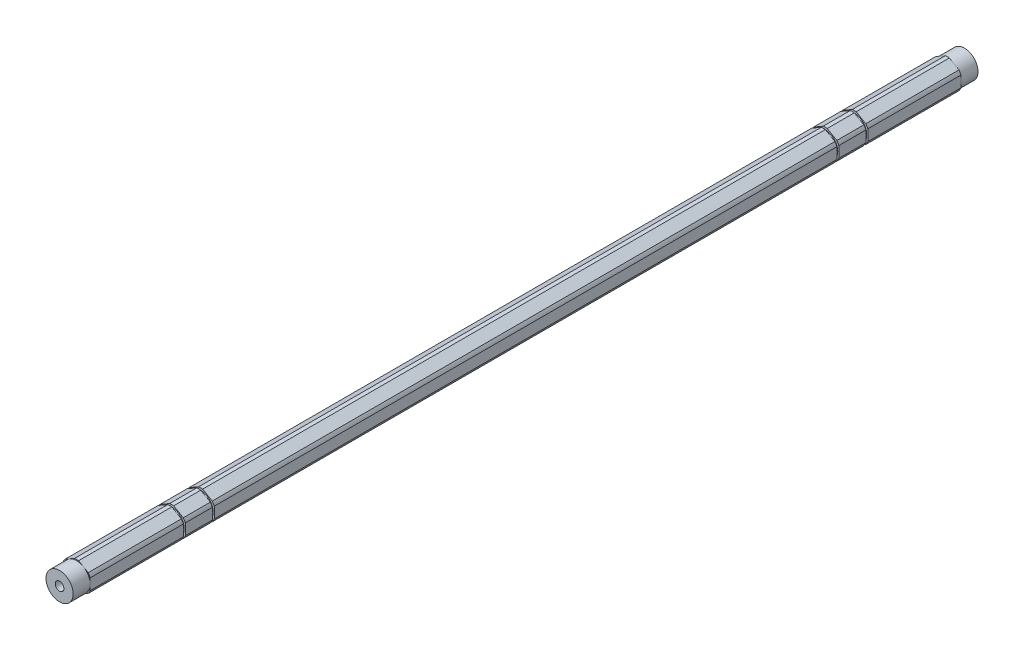
SolidWorks part; units mm, degrees
ref_plane "Front Plane" through (0, 0, 0) normal (0, 0, 1) x (1, 0, 0)
ref_plane "Top Plane" through (0, 0, 0) normal (0, 1, 0) x (1, 0, 0)
ref_plane "Right Plane" through (0, 0, 0) normal (1, 0, 0) x (0, 0, -1)
sketch "Sketch1" plane through (0, 0, 0) normal (0, 0, 1) x (1, 0, 0)
  line L1 (0, 7.3323) -> (-6.35, 3.6662)
  line L2 (-6.35, 3.6662) -> (-6.35, -3.6662)
  line L3 (-6.35, -3.6662) -> (0, -7.3323)
  line L4 (0, -7.3323) -> (6.35, -3.6662)
  line L5 (6.35, -3.6662) -> (6.35, 3.6662)
  line L6 (6.35, 3.6662) -> (0, 7.3323)
  circle A0 centre (0, 0) radius 6.35 construction
  circle A1 centre (0, 0) radius 6.858
  dimension "D1" = 12.7
  dimension "D2" = 13.716
extrude "Boss-Extrude1" add sketch "Sketch1" along normal mid plane 406.4 contours L5 A1 L6 L1 L2 L3 L4 region at (0, 0, 0)
sketch "Sketch6" plane through (0, 0, 203.2) normal (0, 0, 1) x (1, 0, 0)
  line L0 (5.4183, 4.2041) -> (0.9317, 6.7944) construction
  circle A0 centre (0, 0) radius 6.35
extrude "Boss-Extrude2" add sketch "Sketch6" along normal blind 7.9375
mirror "Mirror2" about plane through (0, 0, 0) normal (0, 0, 1) of "Boss-Extrude2"
hole_wizard "#10-32 Tapped Hole1" positions "3DSketch1" profile "Sketch2" tap size "#10-32" standard "ANSI Inch"
sketch3d "3DSketch1"
  line L0 (0, 0, 211.1375) -> (0, 0, 203.2) construction
  line L1 (0, 0, -211.1375) -> (0, 0, -203.2) construction
  point P11 (0, 0, 211.1375)
  point P15 (0, 0, -211.1375)
sketch "Sketch2" plane through (0, 0, 211.1375) normal (1, 0, 0) x (0, -1, 0)
  line L0 (0, 0) -> (0, 17.5608)
  line L1 (0, 17.5608) -> (2.0193, 16.3474)
  line L2 (2.0193, 16.3474) -> (2.0193, 0)
  line L5 (2.0193, 0) -> (0, 0)
  line L10 (0, 17.5608) -> (-2.0193, 16.3474) construction
  line L11 (0, -6.35) -> (0, 107.95) construction
  dimension "Tap Drill Dia." = 4.0386
  dimension "Tap Drill Depth" = 16.3474
  dimension "Drill Angle" = 118
cosmetic thread "Hole Thread1" parameters "D1"=13.97, "D2"=4.826
cosmetic thread "Hole Thread2" parameters "D1"=13.97, "D2"=4.826
sketch "Sketch5" plane through (0, 0, 0) normal (1, 0, 0) x (0, 0, -1)
  line L0 (203.2, 6.858) -> (-203.2, 6.858) construction
  line L1 (-159.7076, 6.858) -> (-158.8186, 6.858)
  line L2 (-159.7076, 6.858) -> (-159.7076, 5.8547)
  line L3 (-159.7076, 5.8547) -> (-158.8186, 5.8547)
  line L4 (-158.8186, 6.858) -> (-158.8186, 5.8547)
  line L5 (-165.0472, 0) -> (-158.8423, 0) construction
  line L6 (-146.1821, 6.858) -> (-145.2931, 6.858)
  line L7 (-146.1821, 6.858) -> (-146.1821, 5.8547)
  line L8 (-146.1821, 5.8547) -> (-145.2931, 5.8547)
  line L9 (-145.2931, 6.858) -> (-145.2931, 5.8547)
  dimension "D1" = 5.8547
  dimension "D2" = 0.889
  dimension "D3" = 44.3814
  dimension "D4" = 12.6365
revolve "Cut-Revolve1" cut sketch "Sketch5" angle 360 about L5
mirror "Mirror1" about plane through (0, 0, 0) normal (0, 0, 1) of "Cut-Revolve1"
